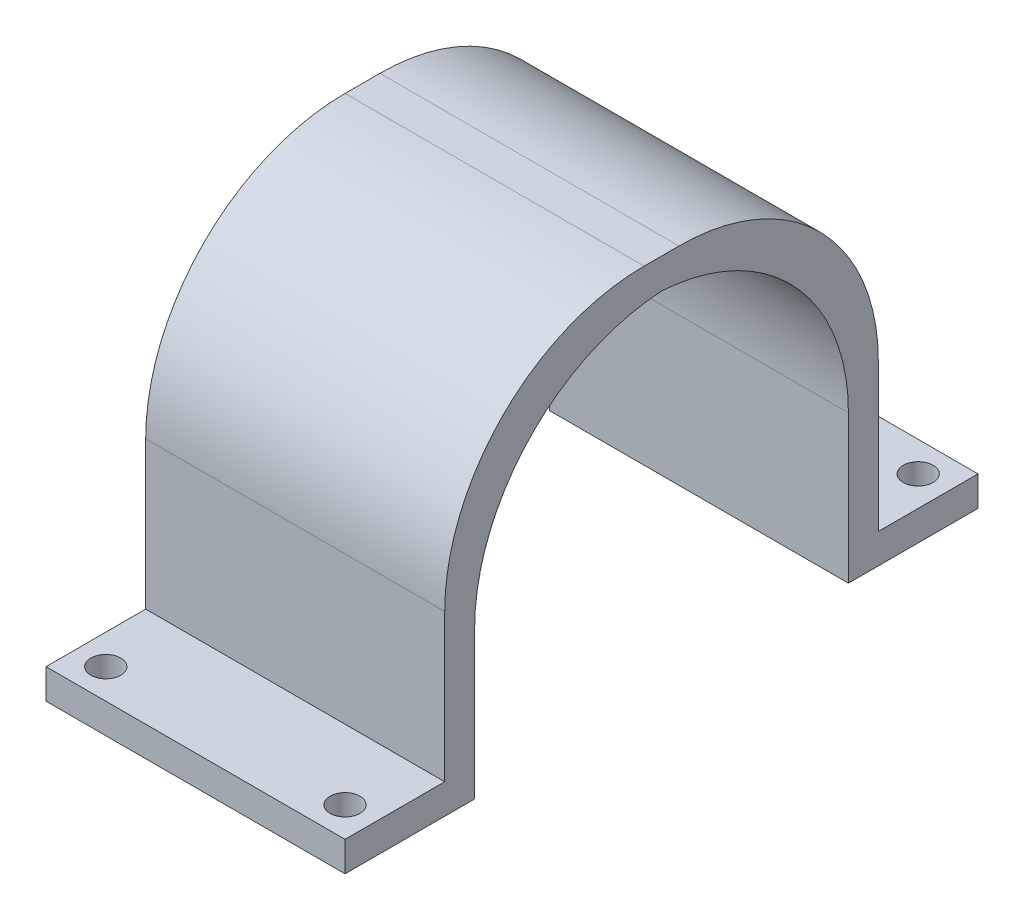
SolidWorks part; units mm, degrees
ref_plane "Front Plane" through (0, 0, 0) normal (0, 0, 1) x (1, 0, 0)
ref_plane "Top Plane" through (0, 0, 0) normal (0, 1, 0) x (1, 0, 0)
ref_plane "Right Plane" through (0, 0, 0) normal (1, 0, 0) x (0, 0, -1)
sketch "Sketch6" plane through (0, 0, 0) normal (1, 0, 0) x (0, 0, -1)
  line L0 (0, 0) -> (10, 0)
  line L9 (10, 0) -> (10, 34.8)
  line L10 (10, 34.8) -> (53.5, 34.8)
  line L11 (53.5, 34.8) -> (53.5, 0)
  line L12 (53.5, 0) -> (63.5, 0)
  line L13 (0, -3) -> (13, -3)
  line L14 (13, -3) -> (13, 31.8)
  line L15 (13, 31.8) -> (50.5, 31.8)
  line L16 (50.5, 31.8) -> (50.5, -3)
  line L17 (50.5, -3) -> (63.5, -3)
  line L18 (63.5, -3) -> (63.5, 0)
  line L19 (0, -3) -> (0, 0)
  dimension "D1" = 3
  dimension "D2" = 10
  dimension "D3" = 10
  dimension "D4" = 3
  dimension "D5" = 3
  dimension "D6" = 37.5
  dimension "D7" = 3
  dimension "D8" = 3
  dimension "D9" = 37.8
extrude "Boss-Extrude2" add sketch "Sketch6" along normal blind 30
fillet "Fillet1" radius 20 4 edges at (15, 31.8, -13) (15, 31.8, -50.5) (15, 34.8, -10) (15, 34.8, -53.5)
sketch "Sketch7" plane through (0, 0, 0) normal (0, 1, 0) x (1, 0, 0)
  line L0 (30, 63.5) -> (0, 63.5) construction
  line L1 (0, 63.5) -> (0, 53.5) construction
  line L2 (30, 63.5) -> (30, 53.5) construction
  line L3 (0, 10) -> (0, 0) construction
  line L4 (30, 0) -> (0, 0) construction
  line L6 (30, 10) -> (30, 0) construction
  circle A0 centre (27, 60.5) radius 1.5
  circle A1 centre (3, 60.5) radius 1.5
  circle A2 centre (3, 3) radius 1.5
  circle A3 centre (27, 3) radius 1.5
  dimension "D1" = 3
  dimension "D2" = 3
  dimension "D3" = 3
  dimension "D4" = 3
  dimension "D5" = 3
  dimension "D6" = 3
  dimension "D7" = 3
  dimension "D8" = 3
  dimension "D9" = 3
  dimension "D10" = 3
  dimension "D11" = 3
  dimension "D12" = 3
extrude "Cut-Extrude2" cut sketch "Sketch7" against normal through all
